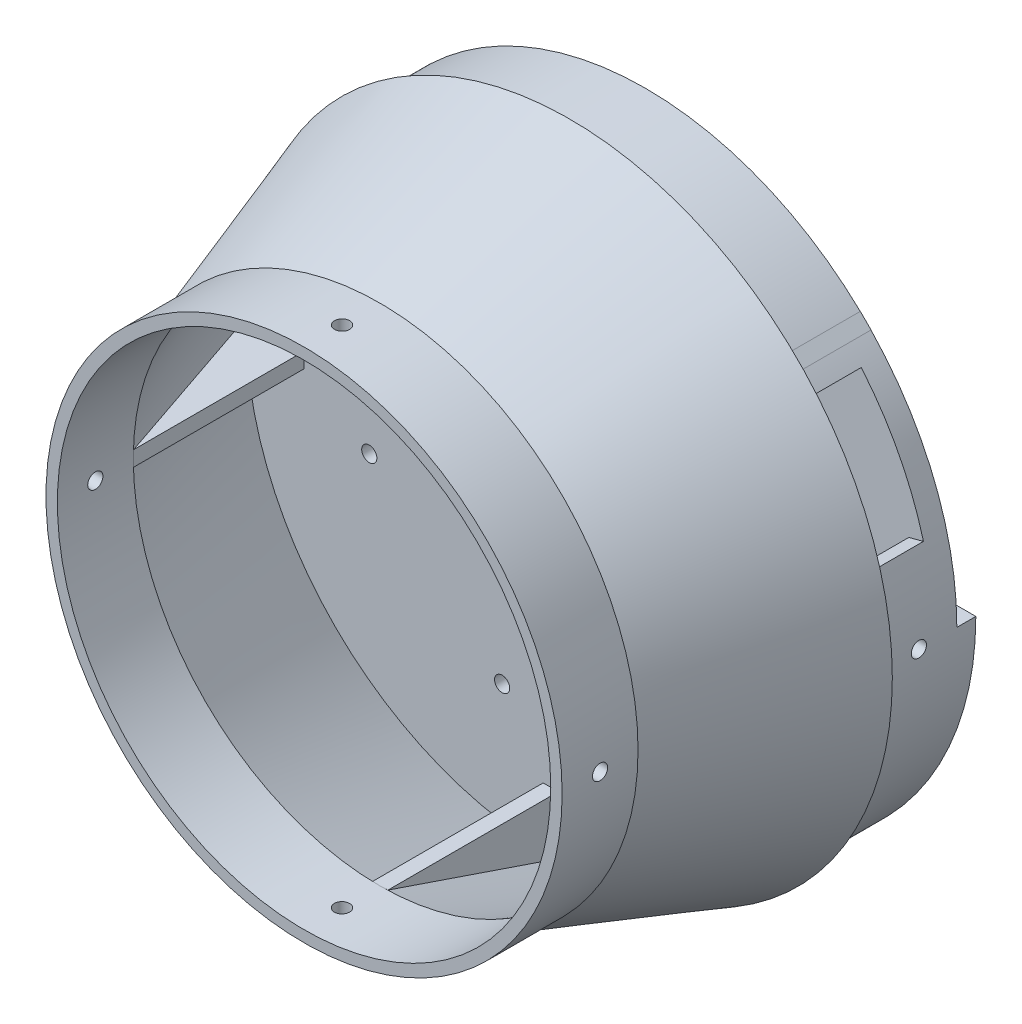
SolidWorks part; units mm, degrees
material "Polyetheretherketone (PEEK)"
ref_plane "Front Plane" through (0, 0, 0) normal (0, 0, 1) x (1, 0, 0)
ref_plane "Top Plane" through (0, 0, 0) normal (0, 1, 0) x (1, 0, 0)
ref_plane "Right Plane" through (0, 0, 0) normal (1, 0, 0) x (0, 0, -1)
sketch "Sketch10" plane through (0, 0, 0) normal (0, 1, 0) x (1, 0, 0)
  line L9 (68, 0) -> (85, 50)
  line L10 (65, 0) -> (65, -20)
  line L11 (65, -20) -> (68, -20)
  line L12 (68, -20) -> (68, 0)
  line L13 (85, 50) -> (0, 50)
  line L14 (0, 50) -> (0, 45)
  line L16 (0, 0) -> (0, 90.5218) construction
  line L17 (65, 0) -> (80.3, 45)
  line L18 (0, 45) -> (80.3, 45)
  dimension "D1" = 65
  dimension "D2" = 20
  dimension "D3" = 50
  dimension "D4" = 85
  dimension "D5" = 68
  dimension "D6" = 5
revolve "Revolve2" add sketch "Sketch10" angle 360 about L16
sketch "Sketch12" plane through (0, 0, 0) normal (0, 1, 0) x (1, 0, 0)
  line L4 (-80.3, 45) -> (-65, 0)
  line L5 (-65, 0) -> (-65, 45)
  line L6 (-80.3, 45) -> (80.3, 45) construction
  line L7 (-65, 45) -> (-80.3, 45)
extrude "Boss-Extrude5" add sketch "Sketch12" along normal blind 2 and the other way blind 2
pattern_circular "CirPattern3" count 4 every 90 about axis through (0, 0, -50) along (0, 0, 1) of "Boss-Extrude5"
sketch "Sketch13" plane through (0, 0, -50) normal (0, 0, -1) x (-1, 0, 0)
  arc A0 (70, 42.7083) -> (70, -42.7083) centre (0, 0) ccw
  arc A1 (70, 34.4093) -> (70, -34.4093) centre (0, 0) ccw
  circle A2 centre (0, 0) radius 82 construction
  circle A3 centre (0, 0) radius 78 construction
  circle A4 centre (0, 0) radius 82
  circle A5 centre (0, 0) radius 78
  dimension "D1" = 164
  dimension "D2" = 4
extrude "Boss-Extrude6" add sketch "Sketch13" along normal blind 20 contours A0 A4 A5 A1 region at (-76.7102, 21.5537, -50)
sketch "Sketch14" plane through (0, 0, 0) normal (0, 1, 0) x (1, 0, 0)
  line L0 (-65, -20) -> (65, -20) construction
  circle A0 centre (0, -10) radius 2
  dimension "D1" = 4
  dimension "D2" = 10
extrude "Cut-Extrude1" cut sketch "Sketch14" against normal blind 95
pattern_circular "CirPattern4" count 4 every 90 about axis through (0, 0, 20) along (0, 0, 1) of "Cut-Extrude1"
sketch "Sketch16" plane through (0, 0, 0) normal (0, 1, 0) x (1, 0, 0)
  line L0 (85, 50) -> (-85, 50) construction
  circle A0 centre (0, 60) radius 2
  dimension "D1" = 4
  dimension "D2" = 10
extrude "Cut-Extrude2" cut sketch "Sketch16" against normal blind 94
pattern_circular "CirPattern5" count 2 every 90 about axis through (0, 0, -70) along (0, 0, -1) of "Cut-Extrude2" other way count 2
sketch "Sketch17" plane through (0, 0, -50) normal (0, 0, -1) x (-1, 0, 0)
  line L0 (0, 0) -> (-47.8133, 12.8115) construction
  line L1 (0, 0) -> (-12.8115, 47.8133) construction
  circle A0 centre (-47.8133, 12.8115) radius 2
  circle A4 centre (-12.8115, 47.8133) radius 2
  circle A5 centre (12.8115, -47.8133) radius 2
  circle A6 centre (47.8133, -12.8115) radius 2
  point P12 (0, 0)
  point P16 (0, 0)
  dimension "D1" = 4
  dimension "D2" = 49.5
  dimension "D4" = 60
  dimension "D3" = 2
  dimension "D5" = 2
extrude "Cut-Extrude4" cut sketch "Sketch17" against normal blind 900
sketch "Sketch19" plane through (0, 0, -70) normal (0, 0, -1) x (-1, 0, 0)
  line L0 (0, 0) -> (0, 85) construction
  line L1 (0, 0) -> (-79.2059, 21.2232)
  line L6 (0, 0) -> (-62.8156, 52.7086)
  circle A0 centre (0, 0) radius 85 construction
  arc A2 (-62.8156, 52.7086) -> (-79.2059, 21.2232) centre (0, 0) ccw
  dimension "D1" = 75
  dimension "D2" = 50
extrude "Cut-Extrude7" cut sketch "Sketch19" against normal blind 20
mirror "Mirror1" about plane through (0, 0, 0) normal (1, 0, 0) of "Cut-Extrude7"
sketch "Sketch22" plane through (0, 0, -70) normal (0, 0, -1) x (-1, 0, 0)
  circle A2 centre (0, 0) radius 82
  circle A3 centre (0, 0) radius 60
  arc M2 (-59.7515, 50.1374) -> (59.7515, 50.1374) centre (0, 0) cw
  line M3 (59.7515, 50.1374) -> (62.8156, 52.7086)
  arc M4 (62.8156, 52.7086) -> (-62.8156, 52.7086) centre (0, 0) ccw
  line M5 (-62.8156, 52.7086) -> (-59.7515, 50.1374)
  dimension "D1" = 120
extrude "Boss-Extrude8" add sketch "Sketch22" against normal blind 6 contours A2 A3 M5 M3 M2 | M5 M2 M3 M4 region at (27.262, -74.9018, -70) region at (-60.4504, 52.4159, -70)
sketch "Sketch24" plane through (0, 0, -50) normal (0, 0, -1) x (-1, 0, 0)
  circle A0 centre (0, 0) radius 25
  dimension "D1" = 50
extrude "Cut-Extrude8" cut sketch "Sketch24" against normal blind 5
ref_plane "Plane1" through (0, 0, 0) normal (-0.7071, 0.7071, 0) x (0.7071, 0.7071, 0)
sketch "Sketch28" plane through (0, 0, 0) normal (-0.7071, 0.7071, 0) x (0.7071, 0.7071, 0)
  line L0 (-68, 50) -> (-68, 70)
  line L1 (82, 70) -> (-82, 70) construction
  line L2 (-68, 70) -> (-82, 70)
  line L3 (-82, 70) -> (-82, 50)
  line L4 (85, 50) -> (-85, 50) construction
  line L5 (-82, 70) -> (-82, 50) construction
  line L6 (-82, 50) -> (-68, 50)
extrude "Boss-Extrude9" add sketch "Sketch28" along normal blind 2 and the other way blind 2
pattern_circular "CirPattern6" count 4 every 90 about axis through (0, 0, -70) along (0, 0, -1) of "Boss-Extrude9"
sketch "Sketch29" plane through (0, 0, -70) normal (0, 0, -1) x (-1, 0, 0)
  line L6 (-75, 0) -> (-82, 0)
  line L8 (75, 0) -> (82, 0)
  arc A0 (-82, 0) -> (82, 0) centre (0, 0) ccw
  arc A2 (-75, 0) -> (75, 0) centre (0, 0) ccw
  dimension "D3" = 150
extrude "Boss-Extrude10" add sketch "Sketch29" along normal blind 5 contours A0 L8 A2 L6
sketch "Sketch30" plane through (0, 0, -50) normal (0, 0, -1) x (-1, 0, 0)
  line L3 (-53.6231, 44.9951) -> (-58.9854, 49.4946)
  line L5 (58.9854, 49.4946) -> (53.6231, 44.9951)
  line L6 (69.7336, 6.1009) -> (76.707, 6.711)
  line L7 (-69.4142, 9.0369) -> (-76.3556, 9.9406)
  line L10 (-69.4142, 9.0369) -> (-76.3556, 9.9406)
  line L12 (-53.6231, 44.9951) -> (-58.9854, 49.4946)
  line L13 (53.6231, 44.9951) -> (58.9854, 49.4946)
  line L14 (69.7336, 6.1009) -> (76.707, 6.711)
  arc A0 (-53.6231, 44.9951) -> (-69.4142, 9.0369) centre (0, 0) ccw
  arc A1 (69.7336, 6.1009) -> (53.6231, 44.9951) centre (0, 0) ccw
  arc A2 (-58.9854, 49.4946) -> (-76.3556, 9.9406) centre (0, 0) ccw
  arc A3 (76.707, 6.711) -> (58.9854, 49.4946) centre (0, 0) ccw
  dimension "D1" = 140
  dimension "D2" = 154
extrude "Cut-Extrude11" cut sketch "Sketch30" against normal blind 10 and the other way blind 10 contours L3 A2 L7 A0 region at (66.4437, 29.1789, -50)
extrude "Cut-Extrude12" cut sketch "Sketch30<5>" against normal blind 10 contours L6 A3 L5 A1 region at (-66.9048, 27.7129, -50)
sketch "Sketch30<5>" plane through (0, 0, -50) normal (0, 0, -1) x (-1, 0, 0) same geometry as "Sketch30"
sketch "Sketch31" plane through (0, 0, -50) normal (0, 0, -1) x (-1, 0, 0)
  line L0 (-75, 0) -> (-82, 0) construction
  line L1 (0, 0) -> (-54.5094, 16.6652)
  line L4 (-54.5094, 16.6652) -> (-38.2522, 11.6949)
  line L5 (-38.2522, 11.6949) -> (-54.5094, 16.6652)
  line L6 (-54.5094, 16.6652) -> (-62.0526, -8.0075)
  line L7 (-54.5094, 16.6652) -> (-38.2522, 11.6949)
  line L8 (-54.5094, 16.6652) -> (-55.3865, 13.7963)
  line L9 (-38.2522, 11.6949) -> (-39.1293, 8.826)
  line L10 (-55.3865, 13.7963) -> (-39.1293, 8.826)
  line L11 (-54.5094, 16.6652) -> (-49.7278, 15.2033)
  line L12 (-54.5094, 16.6652) -> (-52.4628, 23.3593)
  line L13 (-49.7278, 15.2033) -> (-47.6812, 21.8975)
  line L14 (-52.4628, 23.3593) -> (-47.6812, 21.8975)
  line L15 (-62.0526, -8.0075) -> (-41.9702, -14.1473)
  line L16 (-62.0526, -8.0075) -> (-62.9297, -10.8764)
  line L17 (-41.9702, -14.1473) -> (-42.8473, -17.0162)
  line L18 (-62.9297, -10.8764) -> (-42.8473, -17.0162)
  line L19 (-62.9297, -10.8764) -> (-58.1482, -12.3382)
  line L20 (-62.9297, -10.8764) -> (-64.9763, -17.5705)
  line L21 (-58.1482, -12.3382) -> (-60.1948, -19.0324)
  line L22 (-64.9763, -17.5705) -> (-60.1948, -19.0324)
  dimension "D2" = 17
  dimension "D5" = 17
  dimension "D6" = 25.8
  dimension "D7" = 3
  dimension "D8" = 5
  dimension "D9" = 21
  dimension "D10" = 3
  dimension "D11" = 7
  dimension "D12" = 5
  dimension "D13" = 7
extrude "Boss-Extrude11" add sketch "Sketch31" along normal blind 12 contours L14 L12 L7 L13 | L6 L10 L9 L1 L7 | L16 L18 L17 L15 | L20 L22 L21 L18 region at (46.8193, 12.7456, -50) region at (52.4499, -12.5118, -50) region at (51.0953, 19.2813, -50) region at (61.5622, -14.9544, -50)
sketch "Sketch32" plane through (54.5094, 16.6652, 0) normal (0.9563, 0.2924, 0) x (0, 0, -1)
  line L0 (50, -0.4) -> (56.2, -0.4) construction
  line L2 (50, -3) -> (50, 7) construction
  line L3 (56.2, -0.4) -> (56.2, -3) construction
  line L4 (62, -3) -> (50, -3) construction
  circle A0 centre (56.2, -0.4) radius 1.375
  dimension "D1" = 6.2
  dimension "D2" = 2.6
extrude "Cut-Extrude13" cut sketch "Sketch32" against normal blind 10
sketch "Sketch33" plane through (54.5094, 16.6652, 0) normal (0.9563, 0.2924, 0) x (0, 0, -1)
  line L0 (50, -28.4) -> (56.2, -28.4) construction
  line L1 (50, -71.4412) -> (50, -2.8618) construction
  line L2 (62, -25.8) -> (50, -25.8) construction
  circle A0 centre (56.2, -28.4) radius 1.375
  dimension "D1" = 6.2
  dimension "D2" = 2.6
extrude "Cut-Extrude14" cut sketch "Sketch33" against normal blind 10
mirror "Mirror2" about plane through (0, 0, 0) normal (1, 0, 0) of "Cut-Extrude13", "Boss-Extrude11", "Cut-Extrude14"
